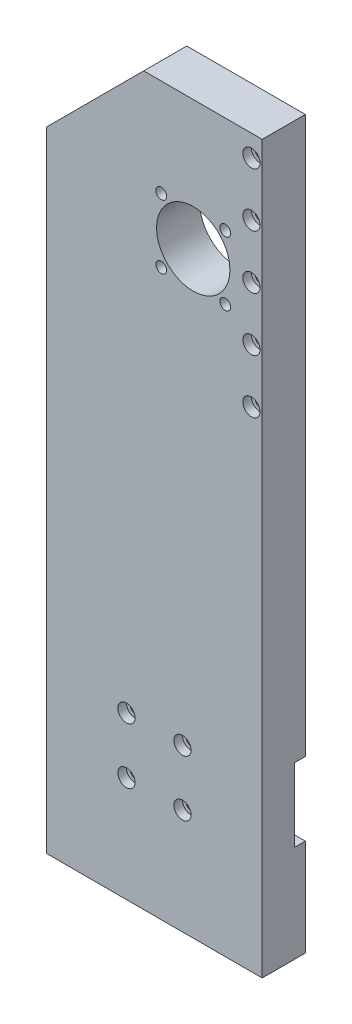
SolidWorks part; units mm, degrees
ref_plane "Front Plane" through (0, 0, 0) normal (0, 0, 1) x (1, 0, 0)
ref_plane "Top Plane" through (0, 0, 0) normal (0, 1, 0) x (1, 0, 0)
ref_plane "Right Plane" through (0, 0, 0) normal (1, 0, 0) x (0, 0, -1)
sketch "Sketch1" plane through (0, 0, 0) normal (0, 0, 1) x (1, 0, 0)
  line L0 (65.7045, 560.5004) -> (50.8553, 575.3496) construction
  line L1 (65.7045, 560.5004) -> (44.7045, 560.5004) construction
  line L2 (65.7045, 560.5004) -> (65.7045, 581.5004) construction
  line L3 (47.7045, 545.8558) -> (47.7045, 439.2537) construction
  line L4 (7.7288, 345.5004) -> (63.5732, 345.5004) construction
  line L5 (97.7045, 283.5004) -> (-2.2955, 283.5004)
  line L6 (97.7045, 283.5004) -> (97.7045, 620.5004)
  line L7 (97.7045, 620.5004) -> (-2.2955, 620.5004)
  line L8 (-2.2955, 283.5004) -> (-2.2955, 620.5004)
  line L9 (97.7045, 283.5004) -> (-2.2955, 620.5004) construction
  line L10 (97.7045, 620.5004) -> (-2.2955, 283.5004) construction
  circle A0 centre (65.7045, 560.5004) radius 17
  circle A1 centre (65.7045, 560.5004) radius 21 construction
  circle A2 centre (80.5538, 575.3496) radius 2.5
  circle A3 centre (80.5538, 545.6511) radius 2.5
  circle A4 centre (50.8553, 545.6511) radius 2.5
  circle A5 centre (50.8553, 575.3496) radius 2.5
  circle A6 centre (34.7045, 358.5004) radius 2
  circle A7 centre (60.7045, 358.5004) radius 2
  circle A8 centre (34.7045, 332.5004) radius 2
  circle A9 centre (60.7045, 332.5004) radius 2
  point P5 (50.8553, 575.3496)
  point P6 (80.5538, 575.3496)
  point P7 (80.5538, 545.6511)
  point P8 (50.8553, 545.6511)
  point P19 (47.7045, 452.0004)
  point P35 (34.7045, 358.5004)
  point P36 (60.7045, 358.5004)
  point P37 (60.7045, 332.5004)
  point P38 (34.7045, 332.5004)
  dimension "D2" = 5
  dimension "D3" = 34
  dimension "D4" = 42
  dimension "D10" = 4
  dimension "D1" = 45
  dimension "D5" = 337
  dimension "D6" = 100
  dimension "D7" = 60
  dimension "D8" = 75
  dimension "D9" = 13
  dimension "D11" = 62
  dimension "D12" = 32
extrude "Boss-Extrude1" add sketch "Sketch1" along normal blind 20
chamfer "Chamfer1" distance 45 angle 45 1 edges at (-2.2955, 620.5004, 10)
sketch "Sketch2" plane through (0, 0, 0) normal (0, 0, 1) x (1, 0, 0)
  line L0 (60.7045, 358.5004) -> (34.7045, 332.5004) construction
  line L1 (34.7045, 358.5004) -> (60.7045, 332.5004) construction
  line L3 (97.7045, 328.5004) -> (-2.2955, 328.5004)
  line L4 (97.7045, 328.5004) -> (97.7045, 362.5004)
  line L5 (97.7045, 362.5004) -> (-2.2955, 362.5004)
  line L6 (-2.2955, 328.5004) -> (-2.2955, 362.5004)
  line L7 (97.7045, 328.5004) -> (-2.2955, 362.5004) construction
  line L8 (97.7045, 362.5004) -> (-2.2955, 328.5004) construction
  point P8 (47.7045, 345.5004)
  point P9 (47.7045, 345.5004)
  dimension "D1" = 100
  dimension "D2" = 34
extrude "Cut-Extrude1" cut sketch "Sketch2" along normal blind 5
sketch "Sketch3" plane through (0, 0, 20) normal (0, 0, 1) x (1, 0, 0)
  line L0 (92.7045, 620.5004) -> (92.7045, 500.5004) construction
  line L1 (97.7045, 620.5004) -> (87.7045, 620.5004) construction
  line L2 (97.7045, 620.5004) -> (97.7045, 500.5004) construction
  line L3 (97.7045, 500.5004) -> (87.7045, 500.5004) construction
  line L4 (87.7045, 620.5004) -> (87.7045, 500.5004) construction
  line L5 (97.7045, 560.5004) -> (87.7045, 560.5004) construction
  point P9 (92.7045, 535.5004)
  point P10 (92.7045, 585.5004)
  point P11 (92.7045, 560.5004)
  point P12 (92.7045, 610.5004)
  point P13 (92.7045, 510.5004)
  dimension "D1" = 10
  dimension "D2" = 120
  dimension "D3" = 3
hole_wizard "CBORE for M4 SHCS1" positions "Sketch5" profile "Sketch6" counterbore size "M4" standard "ANSI Metric" end condition through all
sketch "Sketch5" plane through (0, 0, 20) normal (0, 0, 1) x (1, 0, 0)
  point P0 (92.7045, 610.5004)
  point P5 (92.7045, 585.5004)
  point P8 (92.7045, 560.5004)
  point P11 (92.7045, 535.5004)
  point P14 (92.7045, 510.5004)
sketch "Sketch6" plane through (92.7045, 610.5004, 20) normal (1, 0, 0) x (0, -1, 0)
  line L0 (0, 0) -> (0, 20)
  line L1 (0, 20) -> (2.25, 20)
  line L3 (2.25, 20) -> (2.25, 4)
  line L4 (2.25, 4) -> (4, 4)
  line L5 (4, 4) -> (4, 0)
  line L7 (4, 0) -> (0, 0)
  line L11 (0, -6.35) -> (0, 107.95) construction
  dimension "Thru Hole Dia." = 4.5
  dimension "Thru Hole Depth" = 20
  dimension "C'Bore Dia." = 8
  dimension "C'Bore Depth" = 4
hole_wizard "CBORE for M4 SHCS2" positions "3DSketch2" profile "Sketch10" counterbore size "M4" standard "ANSI Metric" end condition through all
sketch3d "3DSketch2"
  line L0 (34.7045, 358.5004, 20) -> (34.7045, 358.5004, 5) construction
  line L1 (60.7045, 358.5004, 20) -> (60.7045, 358.5004, 5) construction
  line L2 (34.7045, 332.5004, 20) -> (34.7045, 332.5004, 5) construction
  line L3 (60.7045, 332.5004, 20) -> (60.7045, 332.5004, 5) construction
  point P0 (34.7045, 358.5004, 20)
  point P4 (60.7045, 358.5004, 20)
  point P8 (34.7045, 332.5004, 20)
  point P12 (60.7045, 332.5004, 20)
sketch "Sketch10" plane through (34.7045, 358.5004, 20) normal (1, 0, 0) x (0, -1, 0)
  line L0 (0, 0) -> (0, 20)
  line L1 (0, 20) -> (2.25, 20)
  line L3 (2.25, 20) -> (2.25, 4)
  line L4 (2.25, 4) -> (4, 4)
  line L5 (4, 4) -> (4, 0)
  line L7 (4, 0) -> (0, 0)
  line L11 (0, -6.35) -> (0, 107.95) construction
  dimension "Thru Hole Dia." = 4.5
  dimension "Thru Hole Depth" = 20
  dimension "C'Bore Dia." = 8
  dimension "C'Bore Depth" = 4
sketch "Sketch11" plane through (0, 283.5004, 0) normal (0, -1, 0) x (1, 0, 0)
  line L0 (-2.2955, 10) -> (97.7045, 10) construction
  line L1 (-2.2955, 20) -> (-2.2955, 0) construction
  line L2 (97.7045, 20) -> (97.7045, 0) construction
  line L3 (47.7045, 20) -> (47.7045, 0) construction
  line L4 (-2.2955, 20) -> (97.7045, 20) construction
  line L5 (-2.2955, 0) -> (97.7045, 0) construction
  point P12 (67.7045, 10)
  point P13 (87.7045, 10)
  point P14 (47.7045, 10)
  point P15 (7.7045, 10)
  point P16 (27.7045, 10)
  dimension "D1" = 20
  dimension "D2" = 40
hole_wizard "M4 Tapped Hole1" positions "3DSketch3" profile "Sketch12" tap size "M4" standard "ISO"
sketch3d "3DSketch3"
  point P0 (7.7045, 283.5004, 10)
  point P3 (27.7045, 283.5004, 10)
  point P6 (67.7045, 283.5004, 10)
  point P9 (87.7045, 283.5004, 10)
sketch "Sketch12" plane through (7.7045, 283.5004, 10) normal (1, 0, 0) x (0, 0, -1)
  line L0 (0, 0) -> (0, 17.0914)
  line L1 (0, 17.0914) -> (1.65, 16.1)
  line L2 (1.65, 16.1) -> (1.65, 0)
  line L5 (1.65, 0) -> (0, 0)
  line L10 (0, 17.0914) -> (-1.65, 16.1) construction
  line L11 (0, -6.35) -> (0, 107.95) construction
  dimension "Tap Drill Dia." = 3.3
  dimension "Tap Drill Depth" = 16.1
  dimension "Drill Angle" = 118
